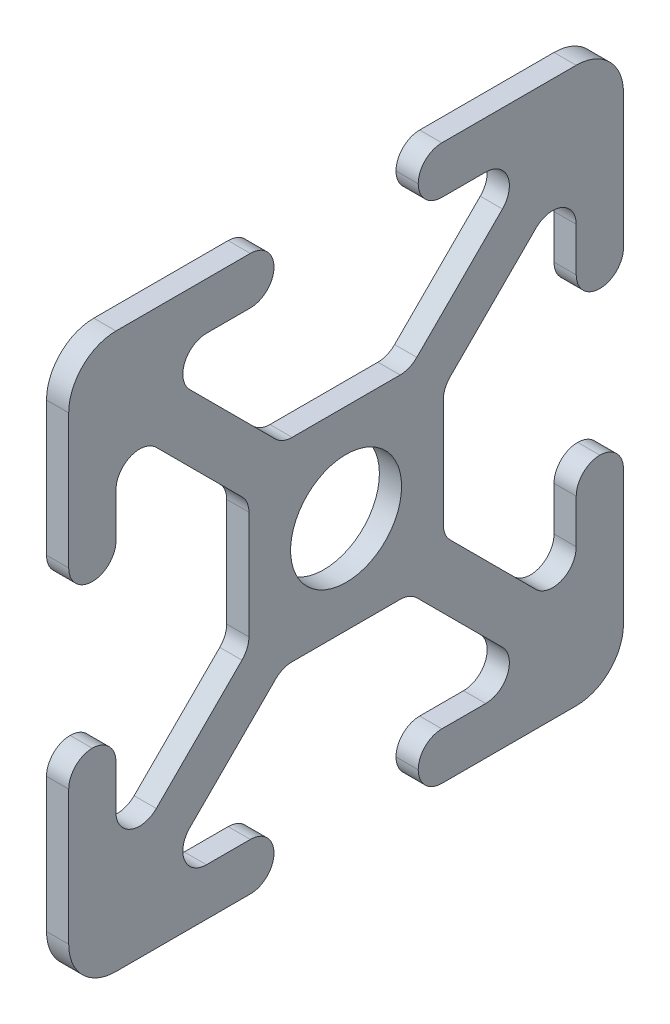
SolidWorks part; units mm, degrees
ref_plane "Front Plane" through (0, 0, 0) normal (1, 0, 0) x (0, 1, 0)
ref_plane "Top Plane" through (0, 0, 0) normal (0, 0, 1) x (0, 1, 0)
ref_plane "Right Plane" through (0, 0, 0) normal (0, 1, 0) x (-1, 0, 0)
sketch "Sketch1" plane through (0, 0, 0) normal (1, 0, 0) x (0, 1, 0)
  line L0 (0, 0) -> (0, 12.5) construction
  line L1 (-12.5, -12.5) -> (12.5, -12.5)
  line L2 (-12.5, -12.5) -> (-12.5, 12.5)
  line L3 (-12.5, 12.5) -> (12.5, 12.5)
  line L4 (12.5, -12.5) -> (12.5, 12.5)
  line L5 (-12.5, -12.5) -> (12.5, 12.5) construction
  line L6 (-12.5, 12.5) -> (12.5, -12.5) construction
  line L7 (-3.25, 12.5) -> (-3.25, 10.37)
  line L8 (-3.25, 10.37) -> (-8.8639, 10.37)
  line L9 (-8.8639, 10.37) -> (-2.8739, 4.38)
  line L10 (-2.8739, 4.38) -> (2.8739, 4.38)
  line L11 (8.8639, 10.37) -> (2.8739, 4.38)
  line L12 (3.25, 10.37) -> (8.8639, 10.37)
  line L13 (3.25, 12.5) -> (3.25, 10.37)
  line L14 (12.5, -3.25) -> (10.37, -3.25)
  line L15 (10.37, -3.25) -> (10.37, -8.8639)
  line L16 (10.37, -8.8639) -> (4.38, -2.8739)
  line L17 (4.38, 2.8739) -> (4.38, -2.8739)
  line L18 (10.37, 8.8639) -> (4.38, 2.8739)
  line L19 (10.37, 3.25) -> (10.37, 8.8639)
  line L20 (12.5, 3.25) -> (10.37, 3.25)
  line L21 (-3.25, -12.5) -> (-3.25, -10.37)
  line L22 (-3.25, -10.37) -> (-8.8639, -10.37)
  line L23 (-8.8639, -10.37) -> (-2.8739, -4.38)
  line L24 (2.8739, -4.38) -> (-2.8739, -4.38)
  line L25 (8.8639, -10.37) -> (2.8739, -4.38)
  line L26 (3.25, -10.37) -> (8.8639, -10.37)
  line L27 (3.25, -12.5) -> (3.25, -10.37)
  line L28 (-12.5, 3.25) -> (-10.37, 3.25)
  line L29 (-10.37, 3.25) -> (-10.37, 8.8639)
  line L30 (-10.37, 8.8639) -> (-4.38, 2.8739)
  line L31 (-4.38, -2.8739) -> (-4.38, 2.8739)
  line L32 (-10.37, -8.8639) -> (-4.38, -2.8739)
  line L33 (-10.37, -3.25) -> (-10.37, -8.8639)
  line L34 (-12.5, -3.25) -> (-10.37, -3.25)
  circle A0 centre (0, 0) radius 2.5
  point P0 (0, 0)
  point P15 (0, 4.38)
  dimension "D3" = 5
  dimension "D1" = 25
  dimension "D2" = 25
  dimension "D4" = 2.13
  dimension "D5" = 2.13
  dimension "D6" = 6.5
  dimension "D7" = 4.38
  dimension "D8" = 4
extrude "Boss-Extrude1" add sketch "Sketch1" along normal blind 1 contours L34 L2 L1 L21 L22 L23 L24 L25 L26 L27 L4 L14 L15 L16 L17 L18 L19 L20 L3 L13 L12 L11 L10 L9 L8 L7 L28 L29 L30 L31 L32 L33 A0 region at (0, -12.1464, -7.875)
fillet "Fillet1" radius 1.065 32 edges at (0.5, -10.37, -8.8639) (0.5, 2.8739, -4.38) (0.5, -2.8739, -4.38) (0.5, -4.38, 2.8739) (0.5, -4.38, -2.8739) (0.5, -2.8739, 4.38) (0.5, 2.8739, 4.38) (0.5, 4.38, 2.8739) (0.5, 4.38, -2.8739) (0.5, -8.8639, -10.37) (0.5, 8.8639, -10.37) (0.5, 10.37, -8.8639) (0.5, -10.37, 8.8639) (0.5, -8.8639, 10.37) (0.5, 10.37, 8.8639) (0.5, 8.8639, 10.37) (0.5, 12.5, 3.25) (0.5, -3.25, -12.5) (0.5, -10.37, 3.25) (0.5, 10.37, 3.25) (0.5, -10.37, -3.25) (0.5, -12.5, -3.25) (0.5, -12.5, 3.25) (0.5, 3.25, -10.37) (0.5, -3.25, -10.37) (0.5, 3.25, -12.5) (0.5, 10.37, -3.25) (0.5, 12.5, -3.25) (0.5, 3.25, 12.5) (0.5, 3.25, 10.37) (0.5, -3.25, 10.37) (0.5, -3.25, 12.5)
fillet "Fillet2" radius 2.13 4 edges at (0.5, 12.5, -12.5) (0.5, -12.5, -12.5) (0.5, 12.5, 12.5) (0.5, -12.5, 12.5)
sketch "Sketch2" plane through (1, 0, 0) normal (1, 0, 0) x (0, 1, 0)
  line L0 (10.37, -12.5) -> (4.315, -12.5)
  line L1 (10.37, -12.5) -> (4.315, -12.5)
  line L2 (4.315, -10.37) -> (6.2927, -10.37)
  line L3 (4.315, -10.37) -> (6.2927, -10.37)
  line L4 (7.0458, -8.5519) -> (3.1858, -4.6919)
  line L5 (7.0458, -8.5519) -> (3.1858, -4.6919)
  line L6 (2.4327, -4.38) -> (-2.4327, -4.38)
  line L7 (2.4327, -4.38) -> (-2.4327, -4.38)
  line L8 (-3.1858, -4.6919) -> (-7.0458, -8.5519)
  line L9 (-3.1858, -4.6919) -> (-7.0458, -8.5519)
  line L10 (-6.2927, -10.37) -> (-4.315, -10.37)
  line L11 (-6.2927, -10.37) -> (-4.315, -10.37)
  line L12 (-4.315, -12.5) -> (-10.37, -12.5)
  line L13 (-4.315, -12.5) -> (-10.37, -12.5)
  line L14 (-12.5, -10.37) -> (-12.5, -4.315)
  line L15 (-12.5, -10.37) -> (-12.5, -4.315)
  line L16 (-10.37, -4.315) -> (-10.37, -6.2927)
  line L17 (-10.37, -4.315) -> (-10.37, -6.2927)
  line L18 (-8.5519, -7.0458) -> (-4.6919, -3.1858)
  line L19 (-8.5519, -7.0458) -> (-4.6919, -3.1858)
  line L20 (-4.38, -2.4327) -> (-4.38, 2.4327)
  line L21 (-4.38, -2.4327) -> (-4.38, 2.4327)
  line L22 (-4.6919, 3.1858) -> (-8.5519, 7.0458)
  line L23 (-4.6919, 3.1858) -> (-8.5519, 7.0458)
  line L24 (-10.37, 6.2927) -> (-10.37, 4.315)
  line L25 (-10.37, 6.2927) -> (-10.37, 4.315)
  line L26 (-12.5, 4.315) -> (-12.5, 10.37)
  line L27 (-12.5, 4.315) -> (-12.5, 10.37)
  line L28 (-10.37, 12.5) -> (-4.315, 12.5)
  line L29 (-10.37, 12.5) -> (-4.315, 12.5)
  line L30 (-4.315, 10.37) -> (-6.2927, 10.37)
  line L31 (-4.315, 10.37) -> (-6.2927, 10.37)
  line L32 (-7.0458, 8.5519) -> (-3.1858, 4.6919)
  line L33 (-7.0458, 8.5519) -> (-3.1858, 4.6919)
  line L34 (-2.4327, 4.38) -> (2.4327, 4.38)
  line L35 (-2.4327, 4.38) -> (2.4327, 4.38)
  line L36 (3.1858, 4.6919) -> (7.0458, 8.5519)
  line L37 (3.1858, 4.6919) -> (7.0458, 8.5519)
  line L38 (6.2927, 10.37) -> (4.315, 10.37)
  line L39 (6.2927, 10.37) -> (4.315, 10.37)
  line L40 (4.315, 12.5) -> (10.37, 12.5)
  line L41 (4.315, 12.5) -> (10.37, 12.5)
  line L42 (12.5, 10.37) -> (12.5, 4.315)
  line L43 (12.5, 10.37) -> (12.5, 4.315)
  line L44 (10.37, 4.315) -> (10.37, 6.2927)
  line L45 (10.37, 4.315) -> (10.37, 6.2927)
  line L46 (8.5519, 7.0458) -> (4.6919, 3.1858)
  line L47 (8.5519, 7.0458) -> (4.6919, 3.1858)
  line L48 (4.38, 2.4327) -> (4.38, -2.4327)
  line L49 (4.38, 2.4327) -> (4.38, -2.4327)
  line L50 (4.6919, -3.1858) -> (8.5519, -7.0458)
  line L51 (4.6919, -3.1858) -> (8.5519, -7.0458)
  line L52 (10.37, -6.2927) -> (10.37, -4.315)
  line L53 (10.37, -6.2927) -> (10.37, -4.315)
  line L54 (12.5, -4.315) -> (12.5, -10.37)
  line L55 (12.5, -4.315) -> (12.5, -10.37)
  arc A0 (10.37, -12.5) -> (12.5, -10.37) centre (10.37, -10.37) ccw
  circle A1 centre (0, 0) radius 2.5
  circle A2 centre (0, 0) radius 2.5
  arc A3 (10.37, -12.5) -> (12.5, -10.37) centre (10.37, -10.37) ccw
  arc A4 (3.25, -11.435) -> (4.315, -12.5) centre (4.315, -11.435) ccw
  arc A5 (3.25, -11.435) -> (4.315, -12.5) centre (4.315, -11.435) ccw
  arc A6 (4.315, -10.37) -> (3.25, -11.435) centre (4.315, -11.435) ccw
  arc A7 (4.315, -10.37) -> (3.25, -11.435) centre (4.315, -11.435) ccw
  arc A8 (6.2927, -10.37) -> (7.0458, -8.5519) centre (6.2927, -9.305) ccw
  arc A9 (6.2927, -10.37) -> (7.0458, -8.5519) centre (6.2927, -9.305) ccw
  arc A10 (3.1858, -4.6919) -> (2.4327, -4.38) centre (2.4327, -5.445) ccw
  arc A11 (3.1858, -4.6919) -> (2.4327, -4.38) centre (2.4327, -5.445) ccw
  arc A12 (-2.4327, -4.38) -> (-3.1858, -4.6919) centre (-2.4327, -5.445) ccw
  arc A13 (-2.4327, -4.38) -> (-3.1858, -4.6919) centre (-2.4327, -5.445) ccw
  arc A14 (-7.0458, -8.5519) -> (-6.2927, -10.37) centre (-6.2927, -9.305) ccw
  arc A15 (-7.0458, -8.5519) -> (-6.2927, -10.37) centre (-6.2927, -9.305) ccw
  arc A16 (-3.25, -11.435) -> (-4.315, -10.37) centre (-4.315, -11.435) ccw
  arc A17 (-3.25, -11.435) -> (-4.315, -10.37) centre (-4.315, -11.435) ccw
  arc A18 (-4.315, -12.5) -> (-3.25, -11.435) centre (-4.315, -11.435) ccw
  arc A19 (-4.315, -12.5) -> (-3.25, -11.435) centre (-4.315, -11.435) ccw
  arc A20 (-12.5, -10.37) -> (-10.37, -12.5) centre (-10.37, -10.37) ccw
  arc A21 (-12.5, -10.37) -> (-10.37, -12.5) centre (-10.37, -10.37) ccw
  arc A22 (-11.435, -3.25) -> (-12.5, -4.315) centre (-11.435, -4.315) ccw
  arc A23 (-11.435, -3.25) -> (-12.5, -4.315) centre (-11.435, -4.315) ccw
  arc A24 (-10.37, -4.315) -> (-11.435, -3.25) centre (-11.435, -4.315) ccw
  arc A25 (-10.37, -4.315) -> (-11.435, -3.25) centre (-11.435, -4.315) ccw
  arc A26 (-10.37, -6.2927) -> (-8.5519, -7.0458) centre (-9.305, -6.2927) ccw
  arc A27 (-10.37, -6.2927) -> (-8.5519, -7.0458) centre (-9.305, -6.2927) ccw
  arc A28 (-4.6919, -3.1858) -> (-4.38, -2.4327) centre (-5.445, -2.4327) ccw
  arc A29 (-4.6919, -3.1858) -> (-4.38, -2.4327) centre (-5.445, -2.4327) ccw
  arc A30 (-4.38, 2.4327) -> (-4.6919, 3.1858) centre (-5.445, 2.4327) ccw
  arc A31 (-4.38, 2.4327) -> (-4.6919, 3.1858) centre (-5.445, 2.4327) ccw
  arc A32 (-8.5519, 7.0458) -> (-10.37, 6.2927) centre (-9.305, 6.2927) ccw
  arc A33 (-8.5519, 7.0458) -> (-10.37, 6.2927) centre (-9.305, 6.2927) ccw
  arc A34 (-11.435, 3.25) -> (-10.37, 4.315) centre (-11.435, 4.315) ccw
  arc A35 (-11.435, 3.25) -> (-10.37, 4.315) centre (-11.435, 4.315) ccw
  arc A36 (-12.5, 4.315) -> (-11.435, 3.25) centre (-11.435, 4.315) ccw
  arc A37 (-12.5, 4.315) -> (-11.435, 3.25) centre (-11.435, 4.315) ccw
  arc A38 (-10.37, 12.5) -> (-12.5, 10.37) centre (-10.37, 10.37) ccw
  arc A39 (-10.37, 12.5) -> (-12.5, 10.37) centre (-10.37, 10.37) ccw
  arc A40 (-3.25, 11.435) -> (-4.315, 12.5) centre (-4.315, 11.435) ccw
  arc A41 (-3.25, 11.435) -> (-4.315, 12.5) centre (-4.315, 11.435) ccw
  arc A42 (-4.315, 10.37) -> (-3.25, 11.435) centre (-4.315, 11.435) ccw
  arc A43 (-4.315, 10.37) -> (-3.25, 11.435) centre (-4.315, 11.435) ccw
  arc A44 (-6.2927, 10.37) -> (-7.0458, 8.5519) centre (-6.2927, 9.305) ccw
  arc A45 (-6.2927, 10.37) -> (-7.0458, 8.5519) centre (-6.2927, 9.305) ccw
  arc A46 (-3.1858, 4.6919) -> (-2.4327, 4.38) centre (-2.4327, 5.445) ccw
  arc A47 (-3.1858, 4.6919) -> (-2.4327, 4.38) centre (-2.4327, 5.445) ccw
  arc A48 (2.4327, 4.38) -> (3.1858, 4.6919) centre (2.4327, 5.445) ccw
  arc A49 (2.4327, 4.38) -> (3.1858, 4.6919) centre (2.4327, 5.445) ccw
  arc A50 (7.0458, 8.5519) -> (6.2927, 10.37) centre (6.2927, 9.305) ccw
  arc A51 (7.0458, 8.5519) -> (6.2927, 10.37) centre (6.2927, 9.305) ccw
  arc A52 (3.25, 11.435) -> (4.315, 10.37) centre (4.315, 11.435) ccw
  arc A53 (3.25, 11.435) -> (4.315, 10.37) centre (4.315, 11.435) ccw
  arc A54 (4.315, 12.5) -> (3.25, 11.435) centre (4.315, 11.435) ccw
  arc A55 (4.315, 12.5) -> (3.25, 11.435) centre (4.315, 11.435) ccw
  arc A56 (12.5, 10.37) -> (10.37, 12.5) centre (10.37, 10.37) ccw
  arc A57 (12.5, 10.37) -> (10.37, 12.5) centre (10.37, 10.37) ccw
  arc A58 (11.435, 3.25) -> (12.5, 4.315) centre (11.435, 4.315) ccw
  arc A59 (11.435, 3.25) -> (12.5, 4.315) centre (11.435, 4.315) ccw
  arc A60 (10.37, 4.315) -> (11.435, 3.25) centre (11.435, 4.315) ccw
  arc A61 (10.37, 4.315) -> (11.435, 3.25) centre (11.435, 4.315) ccw
  arc A62 (10.37, 6.2927) -> (8.5519, 7.0458) centre (9.305, 6.2927) ccw
  arc A63 (10.37, 6.2927) -> (8.5519, 7.0458) centre (9.305, 6.2927) ccw
  arc A64 (4.6919, 3.1858) -> (4.38, 2.4327) centre (5.445, 2.4327) ccw
  arc A65 (4.6919, 3.1858) -> (4.38, 2.4327) centre (5.445, 2.4327) ccw
  arc A66 (4.38, -2.4327) -> (4.6919, -3.1858) centre (5.445, -2.4327) ccw
  arc A67 (4.38, -2.4327) -> (4.6919, -3.1858) centre (5.445, -2.4327) ccw
  arc A68 (8.5519, -7.0458) -> (10.37, -6.2927) centre (9.305, -6.2927) ccw
  arc A69 (8.5519, -7.0458) -> (10.37, -6.2927) centre (9.305, -6.2927) ccw
  arc A70 (11.435, -3.25) -> (10.37, -4.315) centre (11.435, -4.315) ccw
  arc A71 (11.435, -3.25) -> (10.37, -4.315) centre (11.435, -4.315) ccw
  arc A72 (12.5, -4.315) -> (11.435, -3.25) centre (11.435, -4.315) ccw
  arc A73 (12.5, -4.315) -> (11.435, -3.25) centre (11.435, -4.315) ccw
  dimension "D1" = 0
